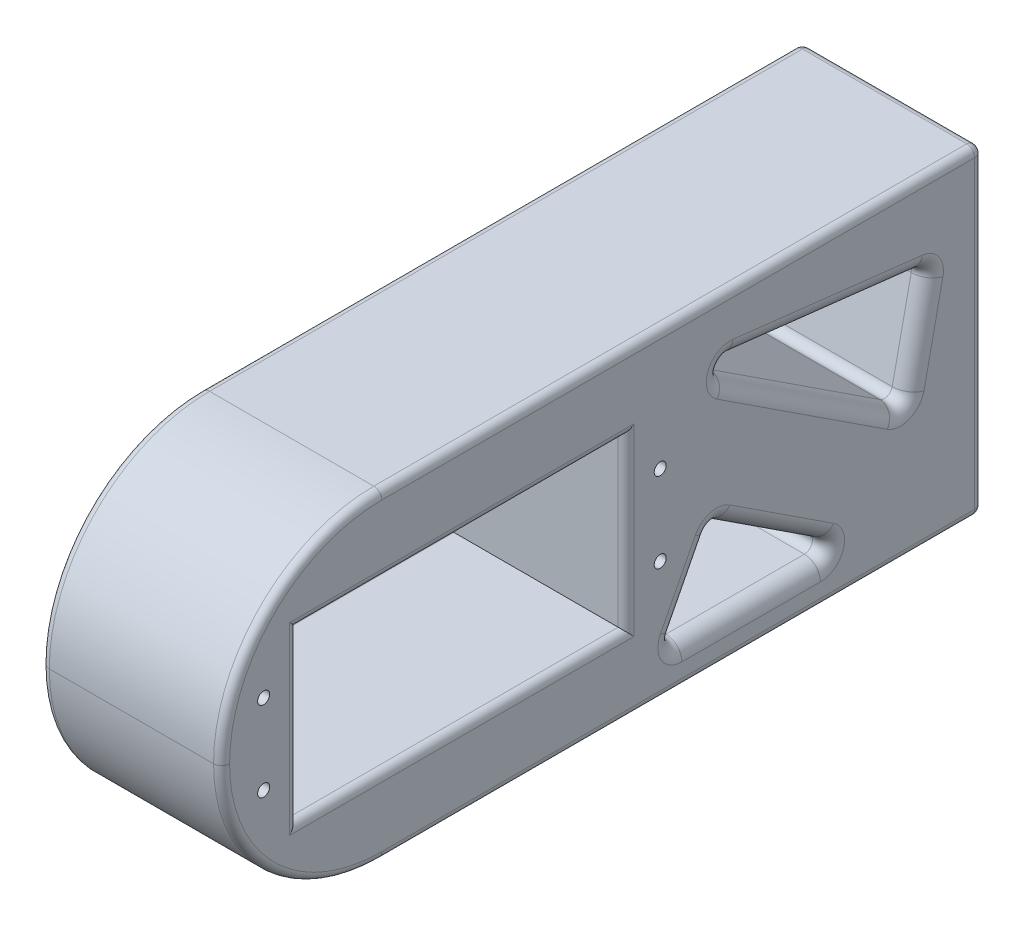
SolidWorks part; units mm, degrees
material "ABS"
ref_plane "Front Plane" through (0, 0, 0) normal (0, 0, 1) x (1, 0, 0)
ref_plane "Top Plane" through (0, 0, 0) normal (0, 1, 0) x (1, 0, 0)
ref_plane "Right Plane" through (0, 0, 0) normal (1, 0, 0) x (0, 0, -1)
sketch "Sketch4" plane through (0, 0, 0) normal (0, 1, 0) x (1, 0, 0)
  line L17 (-16.25, 20) -> (-5, 20)
  line L20 (-5, 20) -> (6.25, 20)
  line L21 (-16.25, -75) -> (-5, -75)
  line L22 (-5, -75) -> (6.25, -75)
  line L23 (6.25, 20) -> (6.25, -75)
  line L24 (-16.25, 20) -> (-16.25, -75)
extrude "MBODY" add sketch "Sketch4" along normal blind 40 contours L17 L20 L23 L22 L21 L24
sketch "Sketch5" plane through (0, 0, -20) normal (0, 0, -1) x (-1, 0, 0)
  line L3 (0, 20) -> (0, 15)
  line L4 (0, 20) -> (0, 25)
  line L5 (0, 25) -> (10, 25)
  line L6 (10, 25) -> (10, 35)
  line L7 (10, 35) -> (0, 35)
  line L8 (0, 15) -> (10, 15)
  line L9 (10, 15) -> (10, 5)
  line L10 (10, 5) -> (0, 5)
  circle A1 centre (0, 5) radius 0.75
  circle A2 centre (10, 5) radius 0.75
  circle A3 centre (10, 15) radius 0.75
  circle A4 centre (0, 15) radius 0.75
  circle A5 centre (0, 25) radius 0.75
  circle A6 centre (10, 25) radius 0.75
  circle A7 centre (10, 35) radius 0.75
  circle A8 centre (0, 35) radius 0.75
extrude "FrontScrews" cut sketch "Sketch5" against normal blind 3 contours A8 | A7 | A6 | A5 | A4 | A3 | A1 | A2
sketch "Sketch7" plane through (0, 0, -20) normal (0, 0, -1) x (-1, 0, 0)
  circle A0 centre (5, 20) radius 2.75
extrude "GUIDKNOB" add sketch "Sketch7" along normal blind 4 contours A0
sketch "Sketch10" plane through (6.25, 0, 0) normal (1, 0, 0) x (0, 0, -1)
  line L1 (-65.5, 20) -> (-65.5, 30.5)
  line L2 (-65.5, 20) -> (-65.5, 9.5)
  line L3 (-65.5, 30.5) -> (-24.5, 30.5)
  line L4 (-65.5, 9.5) -> (-24.5, 9.5)
  line L5 (-24.5, 9.5) -> (-24.5, 30.5)
  point P0 (-45, 30.5)
extrude "ServoCut" cut sketch "Sketch10" against normal blind 40.5 contours L4 L5 L3 L1 L2
fillet "RoundEnd" radius 20 2 edges at (-5, 0, 75) (-5, 40, 75)
sketch "Sketch15" plane through (6.25, 33.75, 0) normal (-1, 0, 0) x (0, 1, 0)
  line L0 (-8.75, -69.75) -> (-8.75, -65)
  line L1 (-18.75, -65) -> (-18.75, -69.75)
  line L2 (-18.75, -69.75) -> (-8.75, -69.75)
  line L3 (-8.75, -20.25) -> (-18.75, -20.25)
  line L6 (-18.75, -25) -> (-18.75, -20.25)
  circle A0 centre (-18.75, -69.75) radius 0.75
  circle A1 centre (-8.75, -69.75) radius 0.75
  circle A2 centre (-8.75, -20.25) radius 0.75
  circle A3 centre (-18.75, -20.25) radius 0.75
extrude "ServoScrews" cut sketch "Sketch15" along normal blind 3 contours A1 | A0 | A2 | A3
fillet "EDGES1MM" radius 1 20 edges at (6.25, 5.8579, 69.1421) (6.25, 34.1421, 69.1421) (-5, 0, -20) (6.25, 0, 17.5) (-5, 40, -20) (6.25, 40, 17.5) (-16.25, 30.5, 45) (-16.25, 20, 24.5) (-16.25, 9.5, 45) (-16.25, 20, 65.5) (-16.25, 20, -20) (-16.25, 40, 17.5) (-16.25, 34.1421, 69.1421) (-16.25, 5.8579, 69.1421) (-16.25, 0, 17.5) (6.25, 9.5, 45) (6.25, 20, 65.5) (6.25, 30.5, 45) (6.25, 20, 24.5) (6.25, 20, -20)
sketch "Sketch20" plane through (-16.25, 0, 0) normal (-1, 0, 0) x (0, 0, 1)
  line L0 (-12.2152, 29.7463) -> (11.3834, 32.4738)
  line L1 (12.0453, 30.6434) -> (-9.1815, 16.7689)
  line L2 (-10.7067, 17.3978) -> (-13.0785, 28.5449)
  line L3 (12.6592, 15.0777) -> (-0.2906, 6.6133)
  line L4 (0.2566, 4.7762) -> (17.5439, 4.7762)
  line L5 (18.4339, 6.2323) -> (14.0963, 14.6967)
  arc A0 (14.0963, 14.6967) -> (12.6592, 15.0777) centre (13.2063, 14.2406) ccw
  arc A1 (17.5439, 4.7762) -> (18.4339, 6.2323) centre (17.5439, 5.7762) ccw
  arc A2 (0.2566, 4.7762) -> (-0.2906, 6.6133) centre (0.2566, 5.7762) cw
  arc A3 (12.0453, 30.6434) -> (11.3834, 32.4738) centre (11.4982, 31.4804) ccw
  arc A4 (-10.7067, 17.3978) -> (-9.1815, 16.7689) centre (-9.7286, 17.6059) ccw
  arc A5 (-13.0785, 28.5449) -> (-12.2152, 29.7463) centre (-12.1004, 28.753) cw
  dimension "D1" = 1
extrude "MASSREDUCTION" cut sketch "Sketch20" against normal blind 25
fillet "MASSREDUCTIONFILLET" radius 2 24 edges at (-16.25, 15.2072, 13.4626) (-16.25, 10.4645, 16.2651) (-16.25, 5.2547, 18.3972) (-16.25, 4.7762, 8.9002) (-16.25, 5.4908, -0.7018) (-16.25, 16.6814, -10.1099) (-16.25, 22.9713, -11.8926) (-16.25, 29.3365, -12.9125) (-16.25, 31.1101, -0.4159) (-16.25, 31.8205, 12.4386) (6.25, 31.8205, 12.4386) (6.25, 31.1101, -0.4159) (6.25, 29.3365, -12.9125) (6.25, 22.9713, -11.8926) (6.25, 16.6814, -10.1099) (6.25, 15.2072, 13.4626) (6.25, 10.8455, 6.1843) (6.25, 5.4908, -0.7018) (6.25, 4.7762, 8.9002) (6.25, 5.2547, 18.3972) (-16.25, 10.8455, 6.1843) (-16.25, 23.7061, 1.4319) (6.25, 23.7061, 1.4319) (6.25, 10.4645, 16.2651)
sketch "Sketch21" plane through (-16.25, 33.75, -16.25) normal (-1, 0, 0) x (0, 1, 0)
  line L0 (-8.75, -86) -> (-8.75, -81.25)
  line L1 (-18.75, -81.25) -> (-18.75, -86)
  line L2 (-18.75, -86) -> (-8.75, -86)
  line L3 (-8.75, -36.5) -> (-18.75, -36.5)
  line L6 (-18.75, -41.25) -> (-18.75, -36.5)
  circle A0 centre (-18.75, -86) radius 0.75
  circle A1 centre (-8.75, -86) radius 0.75
  circle A2 centre (-8.75, -36.5) radius 0.75
  circle A3 centre (-18.75, -36.5) radius 0.75
extrude "ServoScrews1" cut sketch "Sketch21" against normal blind 3 contours A3 | A2 | A0 | A1
equation "\"3.5.00mm\"=5"
